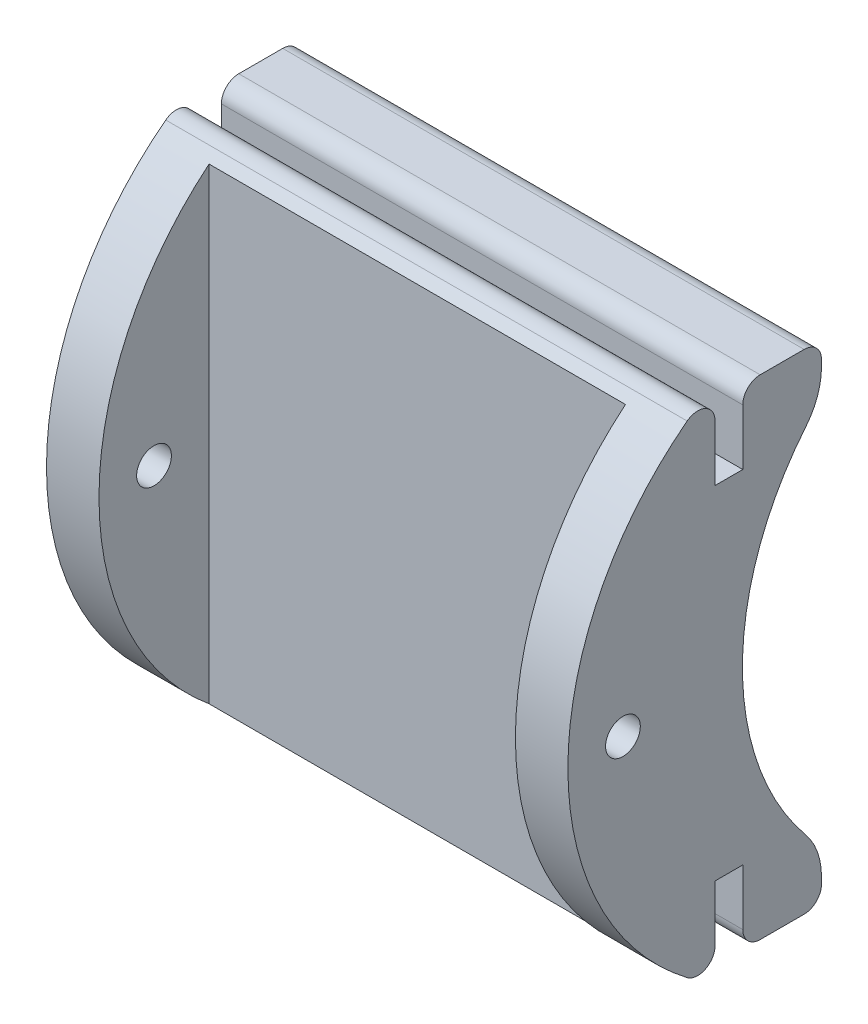
SolidWorks part; units mm, degrees
ref_plane "Front Plane" through (0, 0, 0) normal (1, 0, 0) x (0, 1, 0)
ref_plane "Top Plane" through (0, 0, 0) normal (0, 0, 1) x (0, 1, 0)
ref_plane "Right Plane" through (0, 0, 0) normal (0, 1, 0) x (-1, 0, 0)
sketch "Sketch2" plane through (0, 0, 0) normal (1, 0, 0) x (0, 1, 0)
  line L0 (-63.5, -22.7488) -> (-65.3629, -22.7488)
  line L1 (-70.3629, -17.7488) -> (-70.3629, -5.1018)
  line L2 (-65.3629, -0.1018) -> (-49.26, -0.1018)
  line L3 (-49.26, -0.1018) -> (-49.26, 7.8654)
  line L4 (-49.26, 7.8654) -> (-65.3629, 7.8654)
  line L5 (63.5, -22.7488) -> (65.3629, -22.7488)
  line L6 (70.3629, -17.7488) -> (70.3629, -5.1018)
  line L7 (65.3629, -0.1018) -> (49.26, -0.1018)
  line L8 (49.26, -0.1018) -> (49.26, 7.8654)
  line L9 (49.26, 7.8654) -> (65.3629, 7.8654)
  arc A0 (-50.8, -18.199) -> (50.8, -18.199) centre (0, -80) cw
  arc A1 (-69.3378, 15.8986) -> (69.3378, 15.8986) centre (0, -37.0136) cw
  circle A2 centre (0, 34.375) radius 5
  arc A4 (50.8, -18.199) -> (63.5, -22.7488) centre (63.5, -2.7488) ccw
  arc A5 (-50.8, -18.199) -> (-63.5, -22.7488) centre (-63.5, -2.7488) cw
  arc A6 (65.3629, -22.7488) -> (70.3629, -17.7488) centre (65.3629, -17.7488) ccw
  arc A7 (70.3629, -5.1018) -> (65.3629, -0.1018) centre (65.3629, -5.1018) ccw
  arc A8 (65.3629, 7.8654) -> (69.3378, 15.8986) centre (65.3629, 12.8654) ccw
  arc A9 (-65.3629, 7.8654) -> (-69.3378, 15.8986) centre (-65.3629, 12.8654) cw
  arc A10 (-65.3629, -22.7488) -> (-70.3629, -17.7488) centre (-65.3629, -17.7488) cw
  arc A11 (-70.3629, -5.1018) -> (-65.3629, -0.1018) centre (-65.3629, -5.1018) cw
  point P17 (-50.0392, 8.3432)
  point P18 (-51.3964, -0.1018)
  point P19 (49.26, 8.6312)
  point P20 (0, 0)
  point P21 (69.3378, 15.8986)
  point P22 (0, 34.375)
  point P30 (0, 50.207)
  point P39 (55.8775, -22.7488)
  point P42 (-55.8775, -22.7488)
  dimension "D1" = 80
  dimension "D3" = 10
  dimension "D5" = 5
extrude "Boss-Extrude1" add sketch "Sketch2" along normal blind 150
sketch "Sketch3" plane through (0, 0, 0) normal (0, 1, 0) x (-1, 0, 0)
  line L0 (-150, 39.375) -> (-150, 29.375) construction
  line L1 (-150, 39.375) -> (-150, 29.375)
  line L2 (-1200, 34.375) -> (48800, 34.375) construction
  line L3 (-75, -1065.2015) -> (-75, 48934.7985) construction
  line L4 (-150, -22.7488) -> (0, -22.7488) construction
  line L5 (0, 50.207) -> (-150, 50.207) construction
  line L6 (-15.0975, 18.5431) -> (-134.9025, 18.5431)
  line L7 (-15.0975, 18.5431) -> (-15.0975, 50.207)
  line L8 (-15.0975, 50.207) -> (-134.9025, 50.207)
  line L9 (-134.9025, 18.5431) -> (-134.9025, 50.207)
  line L10 (-15.0975, 18.5431) -> (-134.9025, 50.207) construction
  line L11 (-15.0975, 50.207) -> (-134.9025, 18.5431) construction
  point P5 (-150, 34.375)
  point P6 (-75, 34.375)
  point P10 (-75, -22.7488)
  point P15 (0, 0)
  point P18 (-123.5969, 50.207)
  point P19 (-15.0975, 50.207)
extrude "Cut-Extrude1" cut sketch "Sketch3" against normal through all both and the other way through all contours L7 L8 L9 L6
